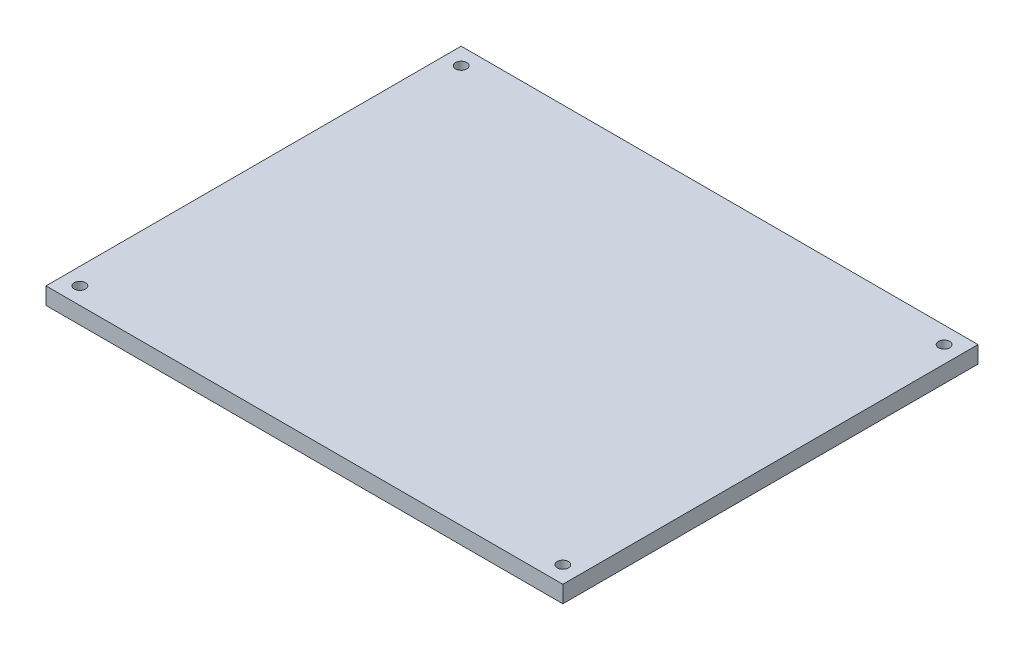
SolidWorks part; units mm, degrees
ref_plane "Front Plane" through (0, 0, 0) normal (0, 0, 1) x (1, 0, 0)
ref_plane "Top Plane" through (0, 0, 0) normal (0, 1, 0) x (1, 0, 0)
ref_plane "Right Plane" through (0, 0, 0) normal (1, 0, 0) x (0, 0, -1)
other "Configuration Table"
sketch "Sketch1" plane through (0, 0, 0) normal (1, 0, 0) x (0, 0, -1)
  line L1 (110, -10) -> (-135, -10)
  line L2 (110, -10) -> (110, 0)
  line L3 (110, 0) -> (-135, 0)
  line L4 (-135, -10) -> (-135, 0)
  line L5 (110, -10) -> (-135, 0) construction
  line L6 (110, 0) -> (-135, -10) construction
  point P0 (-12.5, -5)
extrude "plate" add sketch "Sketch1" along normal blind 305 from offset 40 separate body offset against normal yes
sketch "Sketch2" plane through (0, 0, 0) normal (0, 1, 0) x (1, 0, 0)
  circle A0 centre (-30, 100) radius 3.3
extrude "h0" add sketch "Sketch2" along normal blind 14 from offset 12 separate body offset against normal yes
combine bodies "Combine1" operation type subtract main body 102 bodies to subtract 103
sketch "Sketch3" plane through (0, 0, 0) normal (0, 1, 0) x (1, 0, 0)
  circle A0 centre (-30, -125) radius 3.3
extrude "h1" add sketch "Sketch3" along normal blind 14 from offset 12 separate body offset against normal yes
combine bodies "Combine2" operation type subtract main body 104 bodies to subtract 105
sketch "Sketch4" plane through (0, 0, 0) normal (0, 1, 0) x (1, 0, 0)
  circle A0 centre (255, 100) radius 3.3
extrude "h2" add sketch "Sketch4" along normal blind 14 from offset 12 separate body offset against normal yes
combine bodies "Combine3" operation type subtract main body 106 bodies to subtract 107
sketch "Sketch5" plane through (0, 0, 0) normal (0, 1, 0) x (1, 0, 0)
  circle A0 centre (255, -125) radius 3.3
extrude "h3" add sketch "Sketch5" along normal blind 14 from offset 12 separate body offset against normal yes
combine bodies "Combine4" operation type subtract main body 108 bodies to subtract 109
